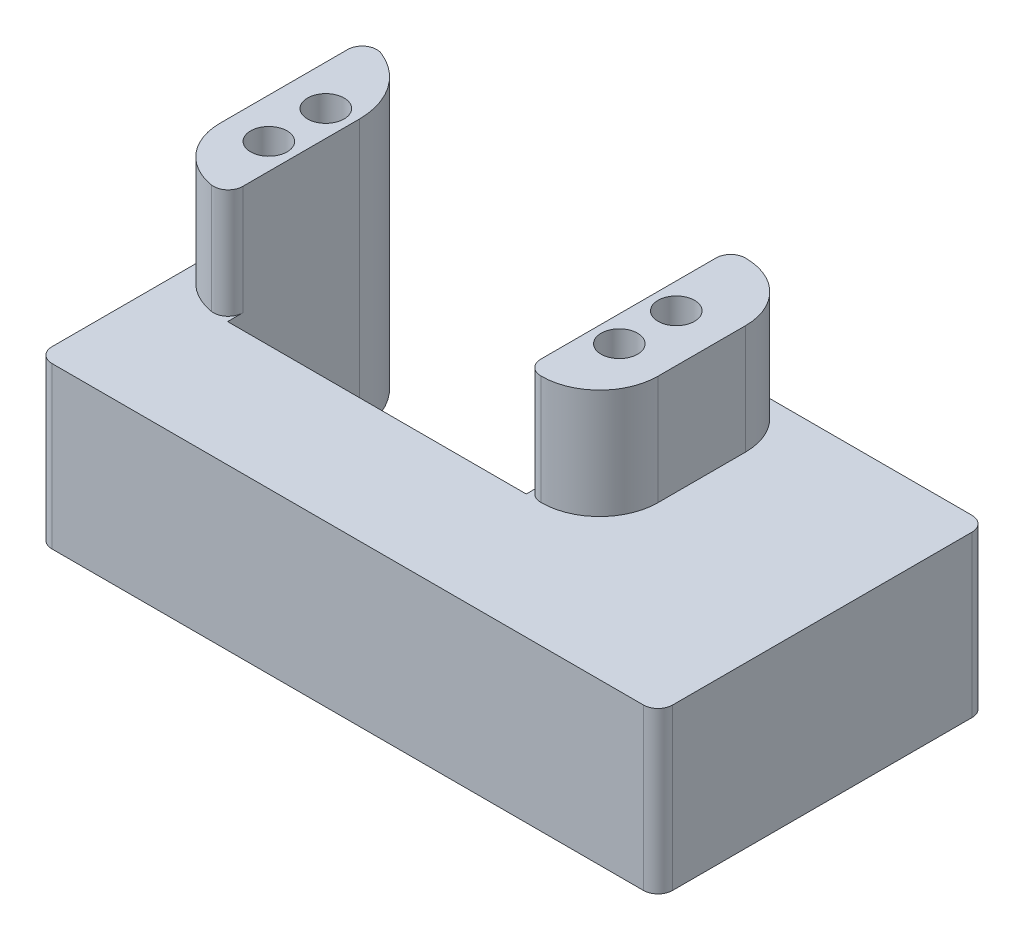
SolidWorks part; units mm, degrees
ref_plane "Front" through (0, 0, 0) normal (0, 0, 1) x (1, 0, 0)
ref_plane "Top" through (0, 0, 0) normal (0, 1, 0) x (1, 0, 0)
ref_plane "Right" through (0, 0, 0) normal (1, 0, 0) x (0, 0, -1)
sketch "Sketch1" plane through (0, 0, 0) normal (0, 1, 0) x (1, 0, 0)
  line L1 (0, 0) -> (85, 0)
  line L2 (0, 0) -> (0, 45)
  line L3 (0, 45) -> (85, 45)
  line L4 (85, 0) -> (85, 45)
  dimension "D1" = 85
  dimension "D2" = 45
extrude "Boss-Extrude1" add sketch "Sketch1" along normal blind 37
sketch "Sketch2" plane through (0, 37, 0) normal (0, 1, 0) x (1, 0, 0)
  line L0 (0, 45) -> (0, 0) construction
  line L1 (85, 45) -> (0, 45) construction
  circle A0 centre (5.5, 34) radius 2.5
  circle A1 centre (53.5, 34) radius 2.5
  circle A2 centre (53.5, 26.2) radius 2.5
  circle A3 centre (5.5, 26.2) radius 2.5
  dimension "D3" = 5
  dimension "D6" = 48
  dimension "D1" = 5.5
  dimension "D2" = 11
  dimension "D7" = 7.8
  dimension "D4" = 2
  dimension "D5" = 2
extrude "Cut-Extrude1" cut sketch "Sketch2" against normal through all
sketch "Sketch4" plane through (0, 0, 0) normal (-1, 0, 0) x (0, 0, 1)
  line L0 (-45, 37) -> (0, 37) construction
  line L1 (0, 37) -> (-17, 37)
  line L2 (0, 37) -> (0, 22)
  line L3 (0, 22) -> (-17, 22)
  line L4 (-17, 37) -> (-17, 22)
  line L5 (0, 37) -> (0, 0) construction
  dimension "D1" = 15
  dimension "D2" = 17
extrude "Cut-Extrude2" cut sketch "Sketch4" against normal through all
sketch "Sketch5" plane through (0, 0, -17) normal (0, 0, 1) x (1, 0, 0)
  line L0 (85, 22) -> (0, 22) construction
  line L1 (85, 37) -> (60, 37)
  line L2 (85, 37) -> (85, 22)
  line L3 (85, 22) -> (60, 22)
  line L4 (60, 37) -> (60, 22)
  dimension "D1" = 25
extrude "Cut-Extrude3" cut sketch "Sketch5" against normal through all
sketch "Sketch6" plane through (0, 37, 0) normal (0, 1, 0) x (1, 0, 0)
  line L0 (60, 17) -> (0, 17) construction
  line L1 (9.05, 17) -> (49.95, 17)
  line L2 (9.05, 17) -> (9.05, 45)
  line L3 (9.05, 45) -> (49.95, 45)
  line L4 (49.95, 17) -> (49.95, 45)
  line L5 (60, 45) -> (0, 45) construction
  line L6 (29.5, 34) -> (29.5, 45) construction
  line L7 (5.5, 34) -> (53.5, 34) construction
  circle A0 centre (5.5, 34) radius 2.5 construction
  dimension "D1" = 3.55
extrude "Cut-Extrude4" cut sketch "Sketch6" against normal through all
fillet "Fillet1" radius 10 1 edges at (9.05, 18.5, -45)
fillet "Fillet2" radius 8 3 edges at (60, 29.5, -45) (0, 29.5, -17) (60, 29.5, -17)
fillet "Fillet4" radius 2 7 edges at (9.05, 29.5, -17) (49.95, 29.5, -17) (49.95, 18.5, -45) (85, 11, -45) (85, 11, 0) (0, 11, 0) (0, 18.5, -45)
